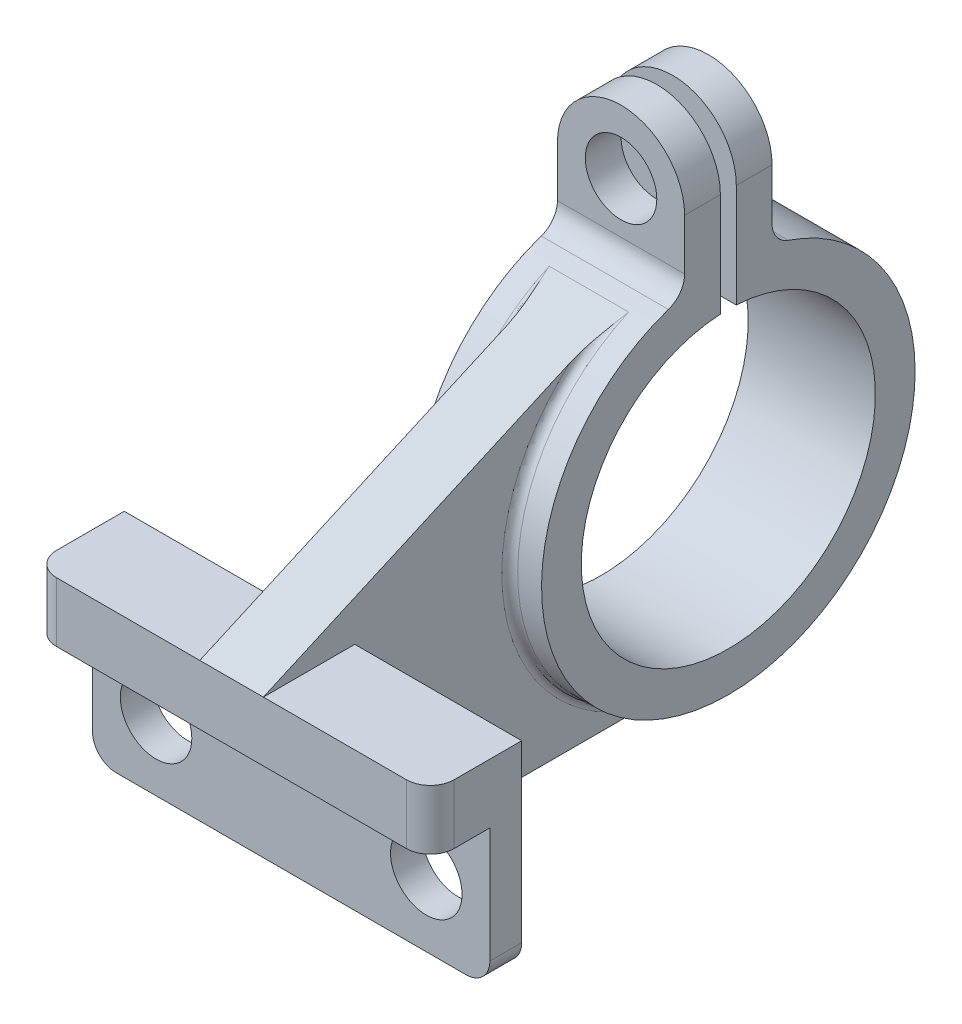
SolidWorks part; units mm, degrees
ref_plane "前基準面" through (0, 0, 0) normal (0, 0, 1) x (1, 0, 0)
ref_plane "上基準面" through (0, 0, 0) normal (0, 1, 0) x (1, 0, 0)
ref_plane "右基準面" through (0, 0, 0) normal (1, 0, 0) x (0, 0, -1)
sketch "草圖1" plane through (0, 0, 0) normal (1, 0, 0) x (0, 0, -1)
  circle A0 centre (0, 0) radius 47
  circle A1 centre (0, 0) radius 37
  dimension "D1" = 94
  dimension "D2" = 74
extrude "填料-伸長1" add sketch "草圖1" along normal blind 32
sketch "草圖2" plane through (32, 0, 0) normal (1, 0, 0) x (0, 0, -1)
  line L0 (-11, 63) -> (-11, 45.6946)
  line L1 (-11, 63) -> (-2, 63)
  line L2 (-2, 63) -> (-2, 46.9574)
  line L3 (0, 37) -> (0, 79.1249) construction
  line L4 (2, 63) -> (2, 46.9574)
  line L5 (11, 63) -> (2, 63)
  line L6 (11, 63) -> (11, 45.6946)
  circle A0 centre (0, 0) radius 47 construction
  arc A1 (-2, 46.9574) -> (-11, 45.6946) centre (0, 0) ccw
  circle A2 centre (0, 0) radius 37 construction
  arc A3 (2, 46.9574) -> (11, 45.6946) centre (0, 0) cw
  dimension "D1" = 22
  dimension "D2" = 4
  dimension "D3" = 63
extrude "填料-伸長2" add sketch "草圖2" against normal up to surface (32 mm away) up to face at (0, 0, -47)
sketch "草圖3" plane through (32, 0, 0) normal (1, 0, 0) x (0, 0, -1)
  line L0 (-2, 46.9574) -> (-2, 63) construction
  line L1 (-2, 50.9595) -> (2, 50.9595)
  line L2 (-2, 50.9595) -> (-2, 30.2437)
  line L3 (-2, 30.2437) -> (2, 30.2437)
  line L4 (2, 50.9595) -> (2, 30.2437)
  line L5 (2, 63) -> (2, 46.9574) construction
extrude "除料-伸長1" cut sketch "草圖3" against normal through all
sketch "草圖4" plane through (0, 0, 11) normal (0, 0, 1) x (1, 0, 0)
  line L0 (0, 63) -> (32, 63) construction
  line L1 (0, 63) -> (32, 63)
  arc A0 (32, 63) -> (0, 63) centre (16, 63) ccw
  circle A1 centre (16, 63) radius 9
  line M6 (32, 63) -> (0, 63)
  dimension "D1" = 18
extrude "填料-伸長3" add sketch "草圖4" against normal blind 9 contours A1 A0 M6 region at (16, 72.3578, 11)
extrude "除料-伸長2" cut sketch "草圖4<3>" against normal blind 9 contours L1 A1 region at (16, 59.1803, 11)
sketch "草圖4<3>" plane through (0, 0, 11) normal (0, 0, 1) x (1, 0, 0) same geometry as "草圖4"
mirror "鏡射1" about plane through (0, 0, 0) normal (0, 0, 1) of "除料-伸長2", "填料-伸長3"
fillet "圓角1" radius 6 2 edges at (16, 45.6946, -11) (16, 45.6946, 11)
ref_plane "平面1" through (16, 0, 0) normal (1, 0, 0) x (0, 0, -1)
sketch "草圖5" plane through (16, 0, 0) normal (1, 0, 0) x (0, 0, -1)
  line L0 (-19.0839, 42.9512) -> (-109, 3)
  line L1 (-109, 3) -> (-86, 3)
  line L2 (-86, 3) -> (-86, -47)
  line L3 (-86, -47) -> (0, -47)
  line L4 (0, 0) -> (0, 3) construction
  arc A0 (-15.0755, 44.5166) -> (15.0755, 44.5166) centre (0, 0) ccw construction
  arc A1 (-15.0755, 44.5166) -> (0, -47) centre (0, 0) ccw
  point P5 (0, 0)
  dimension "D1" = 3
  dimension "D2" = 23
  dimension "D3" = 50
  dimension "D4" = 109
extrude "填料-伸長5" add sketch "草圖5" along normal mid plane 16 contours A1 L0 L1 L2 L3 region at (16, -13.2123, 61.4551)
fillet "圓角3" radius 2 1 edges at (24, -9.7543, 45.9767)
fillet "圓角4" radius 2 1 edges at (8, -9.7543, 45.9767)
ref_plane "平面2" through (66, 0, 0) normal (1, 0, 0) x (0, 0, -1)
sketch "草圖6" plane through (66, 0, 0) normal (1, 0, 0) x (0, 0, -1)
  line L0 (-109, 3) -> (-86, 3)
  line L1 (-86, 3) -> (-86, -47)
  line L2 (-86, -47) -> (-94, -47)
  line L3 (-94, -47) -> (-94, -12)
  line L4 (-94, -12) -> (-109, -12)
  line L5 (-109, -12) -> (-109, 3)
  dimension "D1" = 50
  dimension "D2" = 8
  dimension "D3" = 15
extrude "填料-伸長6" add sketch "草圖6" against normal blind 100
fillet "圓角5" radius 6 2 edges at (-34, -4.5, 109) (66, -4.5, 109)
fillet "圓角6" radius 6 2 edges at (-34, -47, 90) (66, -47, 90)
sketch "草圖7" plane through (0, 0, 94) normal (0, 0, 1) x (1, 0, 0)
  line L0 (16, -12) -> (16, -56.6342) construction
  line L1 (-34, -12) -> (66, -12) construction
  line L2 (-28, -47) -> (60, -47) construction
  circle A0 centre (-18, -30) radius 9
  circle A1 centre (50, -30) radius 9
  dimension "D1" = 68
  dimension "D2" = 18
  dimension "D3" = 17
extrude "除料-伸長3" cut sketch "草圖7" against normal through all
